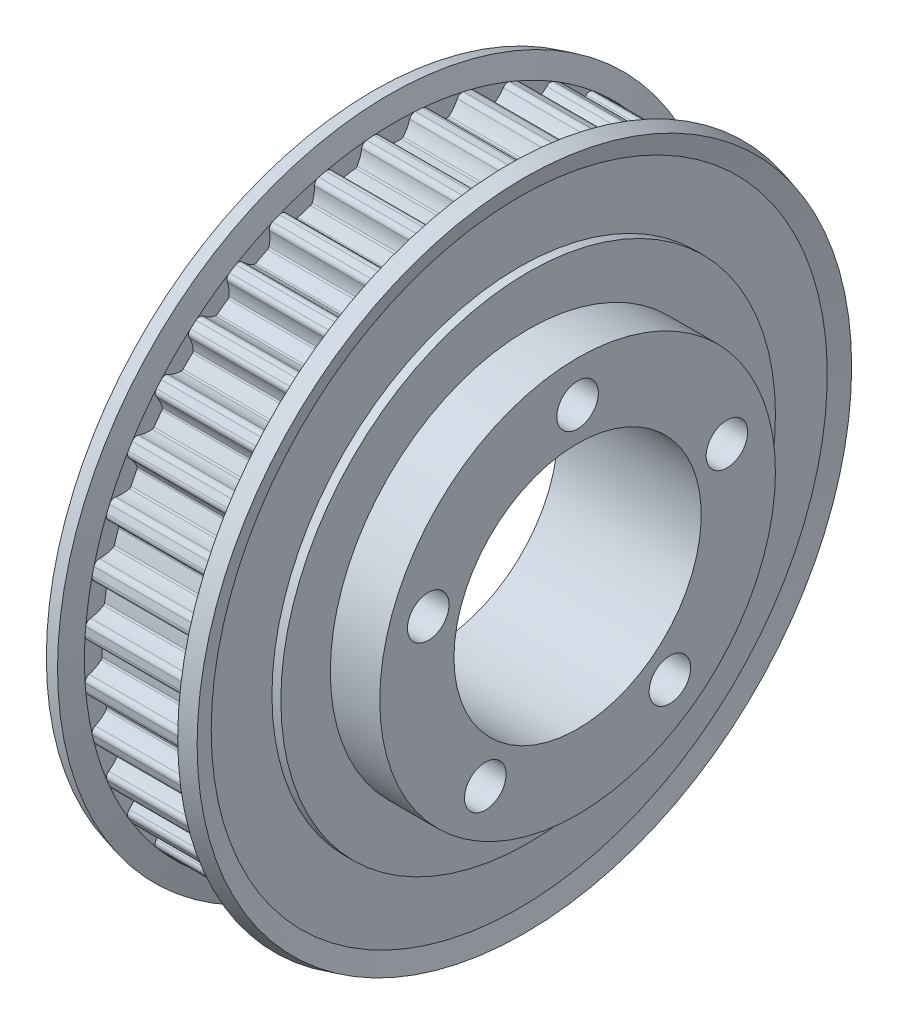
SolidWorks part; units mm, degrees
ref_plane "Front Plane" through (0, 0, 0) normal (0, 0, 1) x (1, 0, 0)
ref_plane "Top Plane" through (0, 0, 0) normal (0, 1, 0) x (1, 0, 0)
ref_plane "Right Plane" through (0, 0, 0) normal (1, 0, 0) x (0, 0, -1)
ref_plane "Plane1" through (0, 0, 0) normal (0, 0, 1) x (1, 0, 0)
sketch "Sketch1" plane through (0, 0, 0) normal (0, 0, 1) x (1, 0, 0)
  line L0 (0, 0) -> (0, 25)
  line L1 (0, 25) -> (0.9, 25)
  line L2 (0.9, 25) -> (0.9, 31.1394)
  line L3 (0.9, 31.1394) -> (0.3784, 33.0859)
  line L4 (0.3784, 33.0859) -> (1.9239, 33.5)
  line L5 (1.9239, 33.5) -> (2.5, 31.35)
  line L6 (2.5, 31.35) -> (13.5, 31.35)
  line L7 (13.5, 31.35) -> (14.0761, 33.5)
  line L8 (14.0761, 33.5) -> (15.6216, 33.0859)
  line L9 (15.6216, 33.0859) -> (15.1, 31.1394)
  line L10 (15.1, 31.1394) -> (15.1, 25)
  line L11 (15.1, 25) -> (16, 25)
  line L12 (16, 25) -> (16, 23.5)
  line L13 (16, 23.5) -> (21, 23.5)
  line L14 (21, 23.5) -> (21, 0)
  line L15 (21, 0) -> (0, 0)
  line L16 (21, 0) -> (0, 0) construction
revolve "Revolve1" add sketch "Sketch1" angle 360 about L16 reverse direction yes
ref_plane "Plane2" through (0, 0, 0) normal (0, 0, 1) x (1, 0, 0)
sketch "Sketch2" plane through (0, 0, 0) normal (0, 0, 1) x (1, 0, 0)
  line L0 (0, 0) -> (0, 12.5)
  line L1 (0, 12.5) -> (21, 12.5)
  line L2 (21, 12.5) -> (21, 0)
  line L3 (21, 0) -> (0, 0)
  line L4 (21, 0) -> (0, 0) construction
revolve "Cut-Revolve1" cut sketch "Sketch2" angle 360 about L4 reverse direction yes
ref_plane "Plane3" through (2.5, 0, 0) normal (1, 0, 0) x (0, 0, -1)
sketch "Sketch3" plane through (2.5, 0, 0) normal (1, 0, 0) x (0, 0, -1)
  line L0 (2.0877, 31.2804) -> (2.0877, 31.7615)
  line L1 (-2.0877, 31.7615) -> (-2.0877, 31.2804)
  arc A0 (-2.0877, 31.2804) -> (-1.5225, 30.8836) centre (-2.0511, 30.7316) cw
  arc A1 (-1.5225, 30.8836) -> (-0.8639, 29.6599) centre (1.625, 31.7885) ccw
  arc A2 (-0.8639, 29.6599) -> (-0.6683, 29.5725) centre (-0.6739, 29.8224) ccw
  arc A3 (-0.6683, 29.5725) -> (0.6683, 29.5725) centre (0, 0) cw
  arc A4 (0.6683, 29.5725) -> (0.8639, 29.6599) centre (0.6739, 29.8224) ccw
  arc A5 (0.8639, 29.6599) -> (1.5225, 30.8836) centre (-1.625, 31.7885) ccw
  arc A6 (1.5225, 30.8836) -> (2.0877, 31.2804) centre (2.0511, 30.7316) cw
  arc A7 (2.0877, 31.7615) -> (-2.0877, 31.7615) centre (0, 0) ccw
extrude "Cut-Extrude1" cut sketch "Sketch3" along normal blind 11
ref_plane "Plane4" through (2.5, 0, 0) normal (1, 0, 0) x (0, 0, -1)
sketch "Sketch4" plane through (2.5, 0, 0) normal (1, 0, 0) x (0, 0, -1)
  line L0 (6.9554, 30.5687) -> (7.0306, 31.0438)
  line L1 (2.9066, 31.697) -> (2.8313, 31.2219)
  arc A0 (2.8313, 31.2219) -> (3.3275, 30.7415) centre (2.7816, 30.6741) cw
  arc A1 (3.3275, 30.7415) -> (3.7865, 29.4299) centre (6.5778, 31.1429) ccw
  arc A2 (3.7865, 29.4299) -> (3.9661, 29.3129) centre (3.9996, 29.5606) ccw
  arc A3 (3.9661, 29.3129) -> (5.2862, 29.1038) centre (0, 0) cw
  arc A4 (5.2862, 29.1038) -> (5.4931, 29.1596) centre (5.3309, 29.3498) ccw
  arc A5 (5.4931, 29.1596) -> (6.335, 30.2652) centre (3.3678, 31.6513) ccw
  arc A6 (6.335, 30.2652) -> (6.9554, 30.5687) centre (6.8333, 30.0324) cw
  arc A7 (7.0306, 31.0438) -> (2.9066, 31.697) centre (0, 0) ccw
extrude "Cut-Extrude2" cut sketch "Sketch4" along normal blind 11
ref_plane "Plane5" through (2.5, 0, 0) normal (1, 0, 0) x (0, 0, -1)
sketch "Sketch5" plane through (2.5, 0, 0) normal (1, 0, 0) x (0, 0, -1)
  line L0 (11.6517, 29.1043) -> (11.8004, 29.5618)
  line L1 (7.8293, 30.8521) -> (7.6806, 30.3946)
  arc A0 (7.6806, 30.3946) -> (8.0956, 29.8425) centre (7.5459, 29.8613) cw
  arc A1 (8.0956, 29.8425) -> (8.3438, 28.4752) centre (11.3687, 29.7305) ccw
  arc A2 (8.3438, 28.4752) -> (8.5028, 28.3316) centre (8.5747, 28.571) ccw
  arc A3 (8.5028, 28.3316) -> (9.774, 27.9186) centre (0, 0) cw
  arc A4 (9.774, 27.9186) -> (9.987, 27.9413) centre (9.8566, 28.1545) ccw
  arc A5 (9.987, 27.9413) -> (10.9915, 28.9016) centre (8.2777, 30.7348) ccw
  arc A6 (10.9915, 28.9016) -> (11.6517, 29.1043) centre (11.4473, 28.5937) cw
  arc A7 (11.8004, 29.5618) -> (7.8293, 30.8521) centre (0, 0) ccw
extrude "Cut-Extrude3" cut sketch "Sketch5" along normal blind 11
ref_plane "Plane6" through (2.5, 0, 0) normal (1, 0, 0) x (0, 0, -1)
sketch "Sketch6" plane through (2.5, 0, 0) normal (1, 0, 0) x (0, 0, -1)
  line L0 (16.0612, 26.9232) -> (16.2796, 27.3519)
  line L1 (12.5592, 29.2475) -> (12.3408, 28.8189)
  arc A0 (12.3408, 28.8189) -> (12.6643, 28.2087) centre (12.1243, 28.3133) cw
  arc A1 (12.6643, 28.2087) -> (12.6956, 26.8194) centre (15.8796, 27.586) ccw
  arc A2 (12.6956, 26.8194) -> (12.8302, 26.6526) centre (12.9386, 26.8779) ccw
  arc A3 (12.8302, 26.6526) -> (14.021, 26.0459) centre (0, 0) cw
  arc A4 (14.021, 26.0459) -> (14.2351, 26.035) centre (14.1396, 26.266) ccw
  arc A5 (14.2351, 26.035) -> (15.3774, 26.8263) centre (12.9838, 29.0615) ccw
  arc A6 (15.3774, 26.8263) -> (16.0612, 26.9232) centre (15.7794, 26.4509) cw
  arc A7 (16.2796, 27.3519) -> (12.5592, 29.2475) centre (0, 0) ccw
extrude "Cut-Extrude4" cut sketch "Sketch6" along normal blind 11
ref_plane "Plane7" through (2.5, 0, 0) normal (1, 0, 0) x (0, 0, -1)
sketch "Sketch7" plane through (2.5, 0, 0) normal (1, 0, 0) x (0, 0, -1)
  line L0 (20.0752, 24.0793) -> (20.3579, 24.4684)
  line L1 (16.9799, 26.9227) -> (16.6972, 26.5335)
  arc A0 (16.6972, 26.5335) -> (16.9212, 25.8803) centre (16.4042, 26.068) cw
  arc A1 (16.9212, 25.8803) -> (16.7347, 24.5032) centre (19.9995, 24.7623) ccw
  arc A2 (16.7347, 24.5032) -> (16.8416, 24.3174) centre (16.9839, 24.5229) ccw
  arc A3 (16.8416, 24.3174) -> (17.9229, 23.5318) centre (0, 0) cw
  arc A4 (17.9229, 23.5318) -> (18.1326, 23.4876) centre (18.0744, 23.7307) ccw
  arc A5 (18.1326, 23.4876) -> (19.3847, 24.0904) centre (17.3702, 26.6726) ccw
  arc A6 (19.3847, 24.0904) -> (20.0752, 24.0793) centre (19.723, 23.6568) cw
  arc A7 (20.3579, 24.4684) -> (16.9799, 26.9227) centre (0, 0) ccw
extrude "Cut-Extrude5" cut sketch "Sketch7" along normal blind 11
ref_plane "Plane8" through (2.5, 0, 0) normal (1, 0, 0) x (0, 0, -1)
sketch "Sketch8" plane through (2.5, 0, 0) normal (1, 0, 0) x (0, 0, -1)
  line L0 (23.5948, 20.6423) -> (23.935, 20.9825)
  line L1 (20.9825, 23.935) -> (20.6423, 23.5948)
  arc A0 (20.6423, 23.5948) -> (20.7614, 22.9146) centre (20.2802, 23.1809) cw
  arc A1 (20.7614, 22.9146) -> (20.3618, 21.5836) centre (23.6269, 21.3288) ccw
  arc A2 (20.3618, 21.5836) -> (20.4383, 21.3834) centre (20.6111, 21.5641) ccw
  arc A3 (20.4383, 21.3834) -> (21.3834, 20.4383) centre (0, 0) cw
  arc A4 (21.3834, 20.4383) -> (21.5836, 20.3618) centre (21.5641, 20.6111) ccw
  arc A5 (21.5836, 20.3618) -> (22.9146, 20.7614) centre (21.3288, 23.6269) ccw
  arc A6 (22.9146, 20.7614) -> (23.5948, 20.6423) centre (23.1809, 20.2802) cw
  arc A7 (23.935, 20.9825) -> (20.9825, 23.935) centre (0, 0) ccw
extrude "Cut-Extrude6" cut sketch "Sketch8" along normal blind 11
ref_plane "Plane9" through (2.5, 0, 0) normal (1, 0, 0) x (0, 0, -1)
sketch "Sketch9" plane through (2.5, 0, 0) normal (1, 0, 0) x (0, 0, -1)
  line L0 (26.5335, 16.6972) -> (26.9227, 16.9799)
  line L1 (24.4684, 20.3579) -> (24.0793, 20.0752)
  arc A0 (24.0793, 20.0752) -> (24.0904, 19.3847) centre (23.6568, 19.723) cw
  arc A1 (24.0904, 19.3847) -> (23.4876, 18.1326) centre (26.6726, 17.3702) ccw
  arc A2 (23.4876, 18.1326) -> (23.5318, 17.9229) centre (23.7307, 18.0744) ccw
  arc A3 (23.5318, 17.9229) -> (24.3174, 16.8416) centre (0, 0) cw
  arc A4 (24.3174, 16.8416) -> (24.5032, 16.7347) centre (24.5229, 16.9839) ccw
  arc A5 (24.5032, 16.7347) -> (25.8803, 16.9212) centre (24.7623, 19.9995) ccw
  arc A6 (25.8803, 16.9212) -> (26.5335, 16.6972) centre (26.068, 16.4042) cw
  arc A7 (26.9227, 16.9799) -> (24.4684, 20.3579) centre (0, 0) ccw
extrude "Cut-Extrude7" cut sketch "Sketch9" along normal blind 11
ref_plane "Plane10" through (2.5, 0, 0) normal (1, 0, 0) x (0, 0, -1)
sketch "Sketch10" plane through (2.5, 0, 0) normal (1, 0, 0) x (0, 0, -1)
  line L0 (28.8189, 12.3408) -> (29.2475, 12.5592)
  line L1 (27.3519, 16.2796) -> (26.9232, 16.0612)
  arc A0 (26.9232, 16.0612) -> (26.8263, 15.3774) centre (26.4509, 15.7794) cw
  arc A1 (26.8263, 15.3774) -> (26.035, 14.2351) centre (29.0615, 12.9838) ccw
  arc A2 (26.035, 14.2351) -> (26.0459, 14.021) centre (26.266, 14.1396) ccw
  arc A3 (26.0459, 14.021) -> (26.6526, 12.8302) centre (0, 0) cw
  arc A4 (26.6526, 12.8302) -> (26.8194, 12.6956) centre (26.8779, 12.9386) ccw
  arc A5 (26.8194, 12.6956) -> (28.2087, 12.6643) centre (27.586, 15.8796) ccw
  arc A6 (28.2087, 12.6643) -> (28.8189, 12.3408) centre (28.3133, 12.1243) cw
  arc A7 (29.2475, 12.5592) -> (27.3519, 16.2796) centre (0, 0) ccw
extrude "Cut-Extrude8" cut sketch "Sketch10" along normal blind 11
ref_plane "Plane11" through (2.5, 0, 0) normal (1, 0, 0) x (0, 0, -1)
sketch "Sketch11" plane through (2.5, 0, 0) normal (1, 0, 0) x (0, 0, -1)
  line L0 (30.3946, 7.6806) -> (30.8521, 7.8293)
  line L1 (29.5618, 11.8004) -> (29.1043, 11.6517)
  arc A0 (29.1043, 11.6517) -> (28.9016, 10.9915) centre (28.5937, 11.4473) cw
  arc A1 (28.9016, 10.9915) -> (27.9413, 9.987) centre (30.7348, 8.2777) ccw
  arc A2 (27.9413, 9.987) -> (27.9186, 9.774) centre (28.1545, 9.8566) ccw
  arc A3 (27.9186, 9.774) -> (28.3316, 8.5028) centre (0, 0) cw
  arc A4 (28.3316, 8.5028) -> (28.4752, 8.3438) centre (28.571, 8.5747) ccw
  arc A5 (28.4752, 8.3438) -> (29.8425, 8.0956) centre (29.7305, 11.3687) ccw
  arc A6 (29.8425, 8.0956) -> (30.3946, 7.6806) centre (29.8613, 7.5459) cw
  arc A7 (30.8521, 7.8293) -> (29.5618, 11.8004) centre (0, 0) ccw
extrude "Cut-Extrude9" cut sketch "Sketch11" along normal blind 11
ref_plane "Plane12" through (2.5, 0, 0) normal (1, 0, 0) x (0, 0, -1)
sketch "Sketch12" plane through (2.5, 0, 0) normal (1, 0, 0) x (0, 0, -1)
  line L0 (31.2219, 2.8313) -> (31.697, 2.9066)
  line L1 (31.0438, 7.0306) -> (30.5687, 6.9554)
  arc A0 (30.5687, 6.9554) -> (30.2652, 6.335) centre (30.0324, 6.8333) cw
  arc A1 (30.2652, 6.335) -> (29.1596, 5.4931) centre (31.6513, 3.3678) ccw
  arc A2 (29.1596, 5.4931) -> (29.1038, 5.2862) centre (29.3498, 5.3309) ccw
  arc A3 (29.1038, 5.2862) -> (29.3129, 3.9661) centre (0, 0) cw
  arc A4 (29.3129, 3.9661) -> (29.4299, 3.7865) centre (29.5606, 3.9996) ccw
  arc A5 (29.4299, 3.7865) -> (30.7415, 3.3275) centre (31.1429, 6.5778) ccw
  arc A6 (30.7415, 3.3275) -> (31.2219, 2.8313) centre (30.6741, 2.7816) cw
  arc A7 (31.697, 2.9066) -> (31.0438, 7.0306) centre (0, 0) ccw
extrude "Cut-Extrude10" cut sketch "Sketch12" along normal blind 11
ref_plane "Plane13" through (2.5, 0, 0) normal (1, 0, 0) x (0, 0, -1)
sketch "Sketch13" plane through (2.5, 0, 0) normal (1, 0, 0) x (0, 0, -1)
  line L0 (31.2804, -2.0877) -> (31.7615, -2.0877)
  line L1 (31.7615, 2.0877) -> (31.2804, 2.0877)
  arc A0 (31.2804, 2.0877) -> (30.8836, 1.5225) centre (30.7316, 2.0511) cw
  arc A1 (30.8836, 1.5225) -> (29.6599, 0.8639) centre (31.7885, -1.625) ccw
  arc A2 (29.6599, 0.8639) -> (29.5725, 0.6683) centre (29.8224, 0.6739) ccw
  arc A3 (29.5725, 0.6683) -> (29.5725, -0.6683) centre (0, 0) cw
  arc A4 (29.5725, -0.6683) -> (29.6599, -0.8639) centre (29.8224, -0.6739) ccw
  arc A5 (29.6599, -0.8639) -> (30.8836, -1.5225) centre (31.7885, 1.625) ccw
  arc A6 (30.8836, -1.5225) -> (31.2804, -2.0877) centre (30.7316, -2.0511) cw
  arc A7 (31.7615, -2.0877) -> (31.7615, 2.0877) centre (0, 0) ccw
extrude "Cut-Extrude11" cut sketch "Sketch13" along normal blind 11
ref_plane "Plane14" through (2.5, 0, 0) normal (1, 0, 0) x (0, 0, -1)
sketch "Sketch14" plane through (2.5, 0, 0) normal (1, 0, 0) x (0, 0, -1)
  line L0 (30.5687, -6.9554) -> (31.0438, -7.0306)
  line L1 (31.697, -2.9066) -> (31.2219, -2.8313)
  arc A0 (31.2219, -2.8313) -> (30.7415, -3.3275) centre (30.6741, -2.7816) cw
  arc A1 (30.7415, -3.3275) -> (29.4299, -3.7865) centre (31.1429, -6.5778) ccw
  arc A2 (29.4299, -3.7865) -> (29.3129, -3.9661) centre (29.5606, -3.9996) ccw
  arc A3 (29.3129, -3.9661) -> (29.1038, -5.2862) centre (0, 0) cw
  arc A4 (29.1038, -5.2862) -> (29.1596, -5.4931) centre (29.3498, -5.3309) ccw
  arc A5 (29.1596, -5.4931) -> (30.2652, -6.335) centre (31.6513, -3.3678) ccw
  arc A6 (30.2652, -6.335) -> (30.5687, -6.9554) centre (30.0324, -6.8333) cw
  arc A7 (31.0438, -7.0306) -> (31.697, -2.9066) centre (0, 0) ccw
extrude "Cut-Extrude12" cut sketch "Sketch14" along normal blind 11
ref_plane "Plane15" through (2.5, 0, 0) normal (1, 0, 0) x (0, 0, -1)
sketch "Sketch15" plane through (2.5, 0, 0) normal (1, 0, 0) x (0, 0, -1)
  line L0 (29.1043, -11.6517) -> (29.5618, -11.8004)
  line L1 (30.8521, -7.8293) -> (30.3946, -7.6806)
  arc A0 (30.3946, -7.6806) -> (29.8425, -8.0956) centre (29.8613, -7.5459) cw
  arc A1 (29.8425, -8.0956) -> (28.4752, -8.3438) centre (29.7305, -11.3687) ccw
  arc A2 (28.4752, -8.3438) -> (28.3316, -8.5028) centre (28.571, -8.5747) ccw
  arc A3 (28.3316, -8.5028) -> (27.9186, -9.774) centre (0, 0) cw
  arc A4 (27.9186, -9.774) -> (27.9413, -9.987) centre (28.1545, -9.8566) ccw
  arc A5 (27.9413, -9.987) -> (28.9016, -10.9915) centre (30.7348, -8.2777) ccw
  arc A6 (28.9016, -10.9915) -> (29.1043, -11.6517) centre (28.5937, -11.4473) cw
  arc A7 (29.5618, -11.8004) -> (30.8521, -7.8293) centre (0, 0) ccw
extrude "Cut-Extrude13" cut sketch "Sketch15" along normal blind 11
ref_plane "Plane16" through (2.5, 0, 0) normal (1, 0, 0) x (0, 0, -1)
sketch "Sketch16" plane through (2.5, 0, 0) normal (1, 0, 0) x (0, 0, -1)
  line L0 (26.9232, -16.0612) -> (27.3519, -16.2796)
  line L1 (29.2475, -12.5592) -> (28.8189, -12.3408)
  arc A0 (28.8189, -12.3408) -> (28.2087, -12.6643) centre (28.3133, -12.1243) cw
  arc A1 (28.2087, -12.6643) -> (26.8194, -12.6956) centre (27.586, -15.8796) ccw
  arc A2 (26.8194, -12.6956) -> (26.6526, -12.8302) centre (26.8779, -12.9386) ccw
  arc A3 (26.6526, -12.8302) -> (26.0459, -14.021) centre (0, 0) cw
  arc A4 (26.0459, -14.021) -> (26.035, -14.2351) centre (26.266, -14.1396) ccw
  arc A5 (26.035, -14.2351) -> (26.8263, -15.3774) centre (29.0615, -12.9838) ccw
  arc A6 (26.8263, -15.3774) -> (26.9232, -16.0612) centre (26.4509, -15.7794) cw
  arc A7 (27.3519, -16.2796) -> (29.2475, -12.5592) centre (0, 0) ccw
extrude "Cut-Extrude14" cut sketch "Sketch16" along normal blind 11
ref_plane "Plane17" through (2.5, 0, 0) normal (1, 0, 0) x (0, 0, -1)
sketch "Sketch17" plane through (2.5, 0, 0) normal (1, 0, 0) x (0, 0, -1)
  line L0 (24.0793, -20.0752) -> (24.4684, -20.3579)
  line L1 (26.9227, -16.9799) -> (26.5335, -16.6972)
  arc A0 (26.5335, -16.6972) -> (25.8803, -16.9212) centre (26.068, -16.4042) cw
  arc A1 (25.8803, -16.9212) -> (24.5032, -16.7347) centre (24.7623, -19.9995) ccw
  arc A2 (24.5032, -16.7347) -> (24.3174, -16.8416) centre (24.5229, -16.9839) ccw
  arc A3 (24.3174, -16.8416) -> (23.5318, -17.9229) centre (0, 0) cw
  arc A4 (23.5318, -17.9229) -> (23.4876, -18.1326) centre (23.7307, -18.0744) ccw
  arc A5 (23.4876, -18.1326) -> (24.0904, -19.3847) centre (26.6726, -17.3702) ccw
  arc A6 (24.0904, -19.3847) -> (24.0793, -20.0752) centre (23.6568, -19.723) cw
  arc A7 (24.4684, -20.3579) -> (26.9227, -16.9799) centre (0, 0) ccw
extrude "Cut-Extrude15" cut sketch "Sketch17" along normal blind 11
ref_plane "Plane18" through (2.5, 0, 0) normal (1, 0, 0) x (0, 0, -1)
sketch "Sketch18" plane through (2.5, 0, 0) normal (1, 0, 0) x (0, 0, -1)
  line L0 (20.6423, -23.5948) -> (20.9825, -23.935)
  line L1 (23.935, -20.9825) -> (23.5948, -20.6423)
  arc A0 (23.5948, -20.6423) -> (22.9146, -20.7614) centre (23.1809, -20.2802) cw
  arc A1 (22.9146, -20.7614) -> (21.5836, -20.3618) centre (21.3288, -23.6269) ccw
  arc A2 (21.5836, -20.3618) -> (21.3834, -20.4383) centre (21.5641, -20.6111) ccw
  arc A3 (21.3834, -20.4383) -> (20.4383, -21.3834) centre (0, 0) cw
  arc A4 (20.4383, -21.3834) -> (20.3618, -21.5836) centre (20.6111, -21.5641) ccw
  arc A5 (20.3618, -21.5836) -> (20.7614, -22.9146) centre (23.6269, -21.3288) ccw
  arc A6 (20.7614, -22.9146) -> (20.6423, -23.5948) centre (20.2802, -23.1809) cw
  arc A7 (20.9825, -23.935) -> (23.935, -20.9825) centre (0, 0) ccw
extrude "Cut-Extrude16" cut sketch "Sketch18" along normal blind 11
ref_plane "Plane19" through (2.5, 0, 0) normal (1, 0, 0) x (0, 0, -1)
sketch "Sketch19" plane through (2.5, 0, 0) normal (1, 0, 0) x (0, 0, -1)
  line L0 (16.6972, -26.5335) -> (16.9799, -26.9227)
  line L1 (20.3579, -24.4684) -> (20.0752, -24.0793)
  arc A0 (20.0752, -24.0793) -> (19.3847, -24.0904) centre (19.723, -23.6568) cw
  arc A1 (19.3847, -24.0904) -> (18.1326, -23.4876) centre (17.3702, -26.6726) ccw
  arc A2 (18.1326, -23.4876) -> (17.9229, -23.5318) centre (18.0744, -23.7307) ccw
  arc A3 (17.9229, -23.5318) -> (16.8416, -24.3174) centre (0, 0) cw
  arc A4 (16.8416, -24.3174) -> (16.7347, -24.5032) centre (16.9839, -24.5229) ccw
  arc A5 (16.7347, -24.5032) -> (16.9212, -25.8803) centre (19.9995, -24.7623) ccw
  arc A6 (16.9212, -25.8803) -> (16.6972, -26.5335) centre (16.4042, -26.068) cw
  arc A7 (16.9799, -26.9227) -> (20.3579, -24.4684) centre (0, 0) ccw
extrude "Cut-Extrude17" cut sketch "Sketch19" along normal blind 11
ref_plane "Plane20" through (2.5, 0, 0) normal (1, 0, 0) x (0, 0, -1)
sketch "Sketch20" plane through (2.5, 0, 0) normal (1, 0, 0) x (0, 0, -1)
  line L0 (12.3408, -28.8189) -> (12.5592, -29.2475)
  line L1 (16.2796, -27.3519) -> (16.0612, -26.9232)
  arc A0 (16.0612, -26.9232) -> (15.3774, -26.8263) centre (15.7794, -26.4509) cw
  arc A1 (15.3774, -26.8263) -> (14.2351, -26.035) centre (12.9838, -29.0615) ccw
  arc A2 (14.2351, -26.035) -> (14.021, -26.0459) centre (14.1396, -26.266) ccw
  arc A3 (14.021, -26.0459) -> (12.8302, -26.6526) centre (0, 0) cw
  arc A4 (12.8302, -26.6526) -> (12.6956, -26.8194) centre (12.9386, -26.8779) ccw
  arc A5 (12.6956, -26.8194) -> (12.6643, -28.2087) centre (15.8796, -27.586) ccw
  arc A6 (12.6643, -28.2087) -> (12.3408, -28.8189) centre (12.1243, -28.3133) cw
  arc A7 (12.5592, -29.2475) -> (16.2796, -27.3519) centre (0, 0) ccw
extrude "Cut-Extrude18" cut sketch "Sketch20" along normal blind 11
ref_plane "Plane21" through (2.5, 0, 0) normal (1, 0, 0) x (0, 0, -1)
sketch "Sketch21" plane through (2.5, 0, 0) normal (1, 0, 0) x (0, 0, -1)
  line L0 (7.6806, -30.3946) -> (7.8293, -30.8521)
  line L1 (11.8004, -29.5618) -> (11.6517, -29.1043)
  arc A0 (11.6517, -29.1043) -> (10.9915, -28.9016) centre (11.4473, -28.5937) cw
  arc A1 (10.9915, -28.9016) -> (9.987, -27.9413) centre (8.2777, -30.7348) ccw
  arc A2 (9.987, -27.9413) -> (9.774, -27.9186) centre (9.8566, -28.1545) ccw
  arc A3 (9.774, -27.9186) -> (8.5028, -28.3316) centre (0, 0) cw
  arc A4 (8.5028, -28.3316) -> (8.3438, -28.4752) centre (8.5747, -28.571) ccw
  arc A5 (8.3438, -28.4752) -> (8.0956, -29.8425) centre (11.3687, -29.7305) ccw
  arc A6 (8.0956, -29.8425) -> (7.6806, -30.3946) centre (7.5459, -29.8613) cw
  arc A7 (7.8293, -30.8521) -> (11.8004, -29.5618) centre (0, 0) ccw
extrude "Cut-Extrude19" cut sketch "Sketch21" along normal blind 11
ref_plane "Plane22" through (2.5, 0, 0) normal (1, 0, 0) x (0, 0, -1)
sketch "Sketch22" plane through (2.5, 0, 0) normal (1, 0, 0) x (0, 0, -1)
  line L0 (2.8313, -31.2219) -> (2.9066, -31.697)
  line L1 (7.0306, -31.0438) -> (6.9554, -30.5687)
  arc A0 (6.9554, -30.5687) -> (6.335, -30.2652) centre (6.8333, -30.0324) cw
  arc A1 (6.335, -30.2652) -> (5.4931, -29.1596) centre (3.3678, -31.6513) ccw
  arc A2 (5.4931, -29.1596) -> (5.2862, -29.1038) centre (5.3309, -29.3498) ccw
  arc A3 (5.2862, -29.1038) -> (3.9661, -29.3129) centre (0, 0) cw
  arc A4 (3.9661, -29.3129) -> (3.7865, -29.4299) centre (3.9996, -29.5606) ccw
  arc A5 (3.7865, -29.4299) -> (3.3275, -30.7415) centre (6.5778, -31.1429) ccw
  arc A6 (3.3275, -30.7415) -> (2.8313, -31.2219) centre (2.7816, -30.6741) cw
  arc A7 (2.9066, -31.697) -> (7.0306, -31.0438) centre (0, 0) ccw
extrude "Cut-Extrude20" cut sketch "Sketch22" along normal blind 11
ref_plane "Plane23" through (2.5, 0, 0) normal (1, 0, 0) x (0, 0, -1)
sketch "Sketch23" plane through (2.5, 0, 0) normal (1, 0, 0) x (0, 0, -1)
  line L0 (-2.0877, -31.2804) -> (-2.0877, -31.7615)
  line L1 (2.0877, -31.7615) -> (2.0877, -31.2804)
  arc A0 (2.0877, -31.2804) -> (1.5225, -30.8836) centre (2.0511, -30.7316) cw
  arc A1 (1.5225, -30.8836) -> (0.8639, -29.6599) centre (-1.625, -31.7885) ccw
  arc A2 (0.8639, -29.6599) -> (0.6683, -29.5725) centre (0.6739, -29.8224) ccw
  arc A3 (0.6683, -29.5725) -> (-0.6683, -29.5725) centre (0, 0) cw
  arc A4 (-0.6683, -29.5725) -> (-0.8639, -29.6599) centre (-0.6739, -29.8224) ccw
  arc A5 (-0.8639, -29.6599) -> (-1.5225, -30.8836) centre (1.625, -31.7885) ccw
  arc A6 (-1.5225, -30.8836) -> (-2.0877, -31.2804) centre (-2.0511, -30.7316) cw
  arc A7 (-2.0877, -31.7615) -> (2.0877, -31.7615) centre (0, 0) ccw
extrude "Cut-Extrude21" cut sketch "Sketch23" along normal blind 11
ref_plane "Plane24" through (2.5, 0, 0) normal (1, 0, 0) x (0, 0, -1)
sketch "Sketch24" plane through (2.5, 0, 0) normal (1, 0, 0) x (0, 0, -1)
  line L0 (-6.9554, -30.5687) -> (-7.0306, -31.0438)
  line L1 (-2.9066, -31.697) -> (-2.8313, -31.2219)
  arc A0 (-2.8313, -31.2219) -> (-3.3275, -30.7415) centre (-2.7816, -30.6741) cw
  arc A1 (-3.3275, -30.7415) -> (-3.7865, -29.4299) centre (-6.5778, -31.1429) ccw
  arc A2 (-3.7865, -29.4299) -> (-3.9661, -29.3129) centre (-3.9996, -29.5606) ccw
  arc A3 (-3.9661, -29.3129) -> (-5.2862, -29.1038) centre (0, 0) cw
  arc A4 (-5.2862, -29.1038) -> (-5.4931, -29.1596) centre (-5.3309, -29.3498) ccw
  arc A5 (-5.4931, -29.1596) -> (-6.335, -30.2652) centre (-3.3678, -31.6513) ccw
  arc A6 (-6.335, -30.2652) -> (-6.9554, -30.5687) centre (-6.8333, -30.0324) cw
  arc A7 (-7.0306, -31.0438) -> (-2.9066, -31.697) centre (0, 0) ccw
extrude "Cut-Extrude22" cut sketch "Sketch24" along normal blind 11
ref_plane "Plane25" through (2.5, 0, 0) normal (1, 0, 0) x (0, 0, -1)
sketch "Sketch25" plane through (2.5, 0, 0) normal (1, 0, 0) x (0, 0, -1)
  line L0 (-11.6517, -29.1043) -> (-11.8004, -29.5618)
  line L1 (-7.8293, -30.8521) -> (-7.6806, -30.3946)
  arc A0 (-7.6806, -30.3946) -> (-8.0956, -29.8425) centre (-7.5459, -29.8613) cw
  arc A1 (-8.0956, -29.8425) -> (-8.3438, -28.4752) centre (-11.3687, -29.7305) ccw
  arc A2 (-8.3438, -28.4752) -> (-8.5028, -28.3316) centre (-8.5747, -28.571) ccw
  arc A3 (-8.5028, -28.3316) -> (-9.774, -27.9186) centre (0, 0) cw
  arc A4 (-9.774, -27.9186) -> (-9.987, -27.9413) centre (-9.8566, -28.1545) ccw
  arc A5 (-9.987, -27.9413) -> (-10.9915, -28.9016) centre (-8.2777, -30.7348) ccw
  arc A6 (-10.9915, -28.9016) -> (-11.6517, -29.1043) centre (-11.4473, -28.5937) cw
  arc A7 (-11.8004, -29.5618) -> (-7.8293, -30.8521) centre (0, 0) ccw
extrude "Cut-Extrude23" cut sketch "Sketch25" along normal blind 11
ref_plane "Plane26" through (2.5, 0, 0) normal (1, 0, 0) x (0, 0, -1)
sketch "Sketch26" plane through (2.5, 0, 0) normal (1, 0, 0) x (0, 0, -1)
  line L0 (-16.0612, -26.9232) -> (-16.2796, -27.3519)
  line L1 (-12.5592, -29.2475) -> (-12.3408, -28.8189)
  arc A0 (-12.3408, -28.8189) -> (-12.6643, -28.2087) centre (-12.1243, -28.3133) cw
  arc A1 (-12.6643, -28.2087) -> (-12.6956, -26.8194) centre (-15.8796, -27.586) ccw
  arc A2 (-12.6956, -26.8194) -> (-12.8302, -26.6526) centre (-12.9386, -26.8779) ccw
  arc A3 (-12.8302, -26.6526) -> (-14.021, -26.0459) centre (0, 0) cw
  arc A4 (-14.021, -26.0459) -> (-14.2351, -26.035) centre (-14.1396, -26.266) ccw
  arc A5 (-14.2351, -26.035) -> (-15.3774, -26.8263) centre (-12.9838, -29.0615) ccw
  arc A6 (-15.3774, -26.8263) -> (-16.0612, -26.9232) centre (-15.7794, -26.4509) cw
  arc A7 (-16.2796, -27.3519) -> (-12.5592, -29.2475) centre (0, 0) ccw
extrude "Cut-Extrude24" cut sketch "Sketch26" along normal blind 11
ref_plane "Plane27" through (2.5, 0, 0) normal (1, 0, 0) x (0, 0, -1)
sketch "Sketch27" plane through (2.5, 0, 0) normal (1, 0, 0) x (0, 0, -1)
  line L0 (-20.0752, -24.0793) -> (-20.3579, -24.4684)
  line L1 (-16.9799, -26.9227) -> (-16.6972, -26.5335)
  arc A0 (-16.6972, -26.5335) -> (-16.9212, -25.8803) centre (-16.4042, -26.068) cw
  arc A1 (-16.9212, -25.8803) -> (-16.7347, -24.5032) centre (-19.9995, -24.7623) ccw
  arc A2 (-16.7347, -24.5032) -> (-16.8416, -24.3174) centre (-16.9839, -24.5229) ccw
  arc A3 (-16.8416, -24.3174) -> (-17.9229, -23.5318) centre (0, 0) cw
  arc A4 (-17.9229, -23.5318) -> (-18.1326, -23.4876) centre (-18.0744, -23.7307) ccw
  arc A5 (-18.1326, -23.4876) -> (-19.3847, -24.0904) centre (-17.3702, -26.6726) ccw
  arc A6 (-19.3847, -24.0904) -> (-20.0752, -24.0793) centre (-19.723, -23.6568) cw
  arc A7 (-20.3579, -24.4684) -> (-16.9799, -26.9227) centre (0, 0) ccw
extrude "Cut-Extrude25" cut sketch "Sketch27" along normal blind 11
ref_plane "Plane28" through (2.5, 0, 0) normal (1, 0, 0) x (0, 0, -1)
sketch "Sketch28" plane through (2.5, 0, 0) normal (1, 0, 0) x (0, 0, -1)
  line L0 (-23.5948, -20.6423) -> (-23.935, -20.9825)
  line L1 (-20.9825, -23.935) -> (-20.6423, -23.5948)
  arc A0 (-20.6423, -23.5948) -> (-20.7614, -22.9146) centre (-20.2802, -23.1809) cw
  arc A1 (-20.7614, -22.9146) -> (-20.3618, -21.5836) centre (-23.6269, -21.3288) ccw
  arc A2 (-20.3618, -21.5836) -> (-20.4383, -21.3834) centre (-20.6111, -21.5641) ccw
  arc A3 (-20.4383, -21.3834) -> (-21.3834, -20.4383) centre (0, 0) cw
  arc A4 (-21.3834, -20.4383) -> (-21.5836, -20.3618) centre (-21.5641, -20.6111) ccw
  arc A5 (-21.5836, -20.3618) -> (-22.9146, -20.7614) centre (-21.3288, -23.6269) ccw
  arc A6 (-22.9146, -20.7614) -> (-23.5948, -20.6423) centre (-23.1809, -20.2802) cw
  arc A7 (-23.935, -20.9825) -> (-20.9825, -23.935) centre (0, 0) ccw
extrude "Cut-Extrude26" cut sketch "Sketch28" along normal blind 11
ref_plane "Plane29" through (2.5, 0, 0) normal (1, 0, 0) x (0, 0, -1)
sketch "Sketch29" plane through (2.5, 0, 0) normal (1, 0, 0) x (0, 0, -1)
  line L0 (-26.5335, -16.6972) -> (-26.9227, -16.9799)
  line L1 (-24.4684, -20.3579) -> (-24.0793, -20.0752)
  arc A0 (-24.0793, -20.0752) -> (-24.0904, -19.3847) centre (-23.6568, -19.723) cw
  arc A1 (-24.0904, -19.3847) -> (-23.4876, -18.1326) centre (-26.6726, -17.3702) ccw
  arc A2 (-23.4876, -18.1326) -> (-23.5318, -17.9229) centre (-23.7307, -18.0744) ccw
  arc A3 (-23.5318, -17.9229) -> (-24.3174, -16.8416) centre (0, 0) cw
  arc A4 (-24.3174, -16.8416) -> (-24.5032, -16.7347) centre (-24.5229, -16.9839) ccw
  arc A5 (-24.5032, -16.7347) -> (-25.8803, -16.9212) centre (-24.7623, -19.9995) ccw
  arc A6 (-25.8803, -16.9212) -> (-26.5335, -16.6972) centre (-26.068, -16.4042) cw
  arc A7 (-26.9227, -16.9799) -> (-24.4684, -20.3579) centre (0, 0) ccw
extrude "Cut-Extrude27" cut sketch "Sketch29" along normal blind 11
ref_plane "Plane30" through (2.5, 0, 0) normal (1, 0, 0) x (0, 0, -1)
sketch "Sketch30" plane through (2.5, 0, 0) normal (1, 0, 0) x (0, 0, -1)
  line L0 (-28.8189, -12.3408) -> (-29.2475, -12.5592)
  line L1 (-27.3519, -16.2796) -> (-26.9232, -16.0612)
  arc A0 (-26.9232, -16.0612) -> (-26.8263, -15.3774) centre (-26.4509, -15.7794) cw
  arc A1 (-26.8263, -15.3774) -> (-26.035, -14.2351) centre (-29.0615, -12.9838) ccw
  arc A2 (-26.035, -14.2351) -> (-26.0459, -14.021) centre (-26.266, -14.1396) ccw
  arc A3 (-26.0459, -14.021) -> (-26.6526, -12.8302) centre (0, 0) cw
  arc A4 (-26.6526, -12.8302) -> (-26.8194, -12.6956) centre (-26.8779, -12.9386) ccw
  arc A5 (-26.8194, -12.6956) -> (-28.2087, -12.6643) centre (-27.586, -15.8796) ccw
  arc A6 (-28.2087, -12.6643) -> (-28.8189, -12.3408) centre (-28.3133, -12.1243) cw
  arc A7 (-29.2475, -12.5592) -> (-27.3519, -16.2796) centre (0, 0) ccw
extrude "Cut-Extrude28" cut sketch "Sketch30" along normal blind 11
ref_plane "Plane31" through (2.5, 0, 0) normal (1, 0, 0) x (0, 0, -1)
sketch "Sketch31" plane through (2.5, 0, 0) normal (1, 0, 0) x (0, 0, -1)
  line L0 (-30.3946, -7.6806) -> (-30.8521, -7.8293)
  line L1 (-29.5618, -11.8004) -> (-29.1043, -11.6517)
  arc A0 (-29.1043, -11.6517) -> (-28.9016, -10.9915) centre (-28.5937, -11.4473) cw
  arc A1 (-28.9016, -10.9915) -> (-27.9413, -9.987) centre (-30.7348, -8.2777) ccw
  arc A2 (-27.9413, -9.987) -> (-27.9186, -9.774) centre (-28.1545, -9.8566) ccw
  arc A3 (-27.9186, -9.774) -> (-28.3316, -8.5028) centre (0, 0) cw
  arc A4 (-28.3316, -8.5028) -> (-28.4752, -8.3438) centre (-28.571, -8.5747) ccw
  arc A5 (-28.4752, -8.3438) -> (-29.8425, -8.0956) centre (-29.7305, -11.3687) ccw
  arc A6 (-29.8425, -8.0956) -> (-30.3946, -7.6806) centre (-29.8613, -7.5459) cw
  arc A7 (-30.8521, -7.8293) -> (-29.5618, -11.8004) centre (0, 0) ccw
extrude "Cut-Extrude29" cut sketch "Sketch31" along normal blind 11
ref_plane "Plane32" through (2.5, 0, 0) normal (1, 0, 0) x (0, 0, -1)
sketch "Sketch32" plane through (2.5, 0, 0) normal (1, 0, 0) x (0, 0, -1)
  line L0 (-31.2219, -2.8313) -> (-31.697, -2.9066)
  line L1 (-31.0438, -7.0306) -> (-30.5687, -6.9554)
  arc A0 (-30.5687, -6.9554) -> (-30.2652, -6.335) centre (-30.0324, -6.8333) cw
  arc A1 (-30.2652, -6.335) -> (-29.1596, -5.4931) centre (-31.6513, -3.3678) ccw
  arc A2 (-29.1596, -5.4931) -> (-29.1038, -5.2862) centre (-29.3498, -5.3309) ccw
  arc A3 (-29.1038, -5.2862) -> (-29.3129, -3.9661) centre (0, 0) cw
  arc A4 (-29.3129, -3.9661) -> (-29.4299, -3.7865) centre (-29.5606, -3.9996) ccw
  arc A5 (-29.4299, -3.7865) -> (-30.7415, -3.3275) centre (-31.1429, -6.5778) ccw
  arc A6 (-30.7415, -3.3275) -> (-31.2219, -2.8313) centre (-30.6741, -2.7816) cw
  arc A7 (-31.697, -2.9066) -> (-31.0438, -7.0306) centre (0, 0) ccw
extrude "Cut-Extrude30" cut sketch "Sketch32" along normal blind 11
ref_plane "Plane33" through (2.5, 0, 0) normal (1, 0, 0) x (0, 0, -1)
sketch "Sketch33" plane through (2.5, 0, 0) normal (1, 0, 0) x (0, 0, -1)
  line L0 (-31.2804, 2.0877) -> (-31.7615, 2.0877)
  line L1 (-31.7615, -2.0877) -> (-31.2804, -2.0877)
  arc A0 (-31.2804, -2.0877) -> (-30.8836, -1.5225) centre (-30.7316, -2.0511) cw
  arc A1 (-30.8836, -1.5225) -> (-29.6599, -0.8639) centre (-31.7885, 1.625) ccw
  arc A2 (-29.6599, -0.8639) -> (-29.5725, -0.6683) centre (-29.8224, -0.6739) ccw
  arc A3 (-29.5725, -0.6683) -> (-29.5725, 0.6683) centre (0, 0) cw
  arc A4 (-29.5725, 0.6683) -> (-29.6599, 0.8639) centre (-29.8224, 0.6739) ccw
  arc A5 (-29.6599, 0.8639) -> (-30.8836, 1.5225) centre (-31.7885, -1.625) ccw
  arc A6 (-30.8836, 1.5225) -> (-31.2804, 2.0877) centre (-30.7316, 2.0511) cw
  arc A7 (-31.7615, 2.0877) -> (-31.7615, -2.0877) centre (0, 0) ccw
extrude "Cut-Extrude31" cut sketch "Sketch33" along normal blind 11
ref_plane "Plane34" through (2.5, 0, 0) normal (1, 0, 0) x (0, 0, -1)
sketch "Sketch34" plane through (2.5, 0, 0) normal (1, 0, 0) x (0, 0, -1)
  line L0 (-30.5687, 6.9554) -> (-31.0438, 7.0306)
  line L1 (-31.697, 2.9066) -> (-31.2219, 2.8313)
  arc A0 (-31.2219, 2.8313) -> (-30.7415, 3.3275) centre (-30.6741, 2.7816) cw
  arc A1 (-30.7415, 3.3275) -> (-29.4299, 3.7865) centre (-31.1429, 6.5778) ccw
  arc A2 (-29.4299, 3.7865) -> (-29.3129, 3.9661) centre (-29.5606, 3.9996) ccw
  arc A3 (-29.3129, 3.9661) -> (-29.1038, 5.2862) centre (0, 0) cw
  arc A4 (-29.1038, 5.2862) -> (-29.1596, 5.4931) centre (-29.3498, 5.3309) ccw
  arc A5 (-29.1596, 5.4931) -> (-30.2652, 6.335) centre (-31.6513, 3.3678) ccw
  arc A6 (-30.2652, 6.335) -> (-30.5687, 6.9554) centre (-30.0324, 6.8333) cw
  arc A7 (-31.0438, 7.0306) -> (-31.697, 2.9066) centre (0, 0) ccw
extrude "Cut-Extrude32" cut sketch "Sketch34" along normal blind 11
ref_plane "Plane35" through (2.5, 0, 0) normal (1, 0, 0) x (0, 0, -1)
sketch "Sketch35" plane through (2.5, 0, 0) normal (1, 0, 0) x (0, 0, -1)
  line L0 (-29.1043, 11.6517) -> (-29.5618, 11.8004)
  line L1 (-30.8521, 7.8293) -> (-30.3946, 7.6806)
  arc A0 (-30.3946, 7.6806) -> (-29.8425, 8.0956) centre (-29.8613, 7.5459) cw
  arc A1 (-29.8425, 8.0956) -> (-28.4752, 8.3438) centre (-29.7305, 11.3687) ccw
  arc A2 (-28.4752, 8.3438) -> (-28.3316, 8.5028) centre (-28.571, 8.5747) ccw
  arc A3 (-28.3316, 8.5028) -> (-27.9186, 9.774) centre (0, 0) cw
  arc A4 (-27.9186, 9.774) -> (-27.9413, 9.987) centre (-28.1545, 9.8566) ccw
  arc A5 (-27.9413, 9.987) -> (-28.9016, 10.9915) centre (-30.7348, 8.2777) ccw
  arc A6 (-28.9016, 10.9915) -> (-29.1043, 11.6517) centre (-28.5937, 11.4473) cw
  arc A7 (-29.5618, 11.8004) -> (-30.8521, 7.8293) centre (0, 0) ccw
extrude "Cut-Extrude33" cut sketch "Sketch35" along normal blind 11
ref_plane "Plane36" through (2.5, 0, 0) normal (1, 0, 0) x (0, 0, -1)
sketch "Sketch36" plane through (2.5, 0, 0) normal (1, 0, 0) x (0, 0, -1)
  line L0 (-26.9232, 16.0612) -> (-27.3519, 16.2796)
  line L1 (-29.2475, 12.5592) -> (-28.8189, 12.3408)
  arc A0 (-28.8189, 12.3408) -> (-28.2087, 12.6643) centre (-28.3133, 12.1243) cw
  arc A1 (-28.2087, 12.6643) -> (-26.8194, 12.6956) centre (-27.586, 15.8796) ccw
  arc A2 (-26.8194, 12.6956) -> (-26.6526, 12.8302) centre (-26.8779, 12.9386) ccw
  arc A3 (-26.6526, 12.8302) -> (-26.0459, 14.021) centre (0, 0) cw
  arc A4 (-26.0459, 14.021) -> (-26.035, 14.2351) centre (-26.266, 14.1396) ccw
  arc A5 (-26.035, 14.2351) -> (-26.8263, 15.3774) centre (-29.0615, 12.9838) ccw
  arc A6 (-26.8263, 15.3774) -> (-26.9232, 16.0612) centre (-26.4509, 15.7794) cw
  arc A7 (-27.3519, 16.2796) -> (-29.2475, 12.5592) centre (0, 0) ccw
extrude "Cut-Extrude34" cut sketch "Sketch36" along normal blind 11
ref_plane "Plane37" through (2.5, 0, 0) normal (1, 0, 0) x (0, 0, -1)
sketch "Sketch37" plane through (2.5, 0, 0) normal (1, 0, 0) x (0, 0, -1)
  line L0 (-24.0793, 20.0752) -> (-24.4684, 20.3579)
  line L1 (-26.9227, 16.9799) -> (-26.5335, 16.6972)
  arc A0 (-26.5335, 16.6972) -> (-25.8803, 16.9212) centre (-26.068, 16.4042) cw
  arc A1 (-25.8803, 16.9212) -> (-24.5032, 16.7347) centre (-24.7623, 19.9995) ccw
  arc A2 (-24.5032, 16.7347) -> (-24.3174, 16.8416) centre (-24.5229, 16.9839) ccw
  arc A3 (-24.3174, 16.8416) -> (-23.5318, 17.9229) centre (0, 0) cw
  arc A4 (-23.5318, 17.9229) -> (-23.4876, 18.1326) centre (-23.7307, 18.0744) ccw
  arc A5 (-23.4876, 18.1326) -> (-24.0904, 19.3847) centre (-26.6726, 17.3702) ccw
  arc A6 (-24.0904, 19.3847) -> (-24.0793, 20.0752) centre (-23.6568, 19.723) cw
  arc A7 (-24.4684, 20.3579) -> (-26.9227, 16.9799) centre (0, 0) ccw
extrude "Cut-Extrude35" cut sketch "Sketch37" along normal blind 11
ref_plane "Plane38" through (2.5, 0, 0) normal (1, 0, 0) x (0, 0, -1)
sketch "Sketch38" plane through (2.5, 0, 0) normal (1, 0, 0) x (0, 0, -1)
  line L0 (-20.6423, 23.5948) -> (-20.9825, 23.935)
  line L1 (-23.935, 20.9825) -> (-23.5948, 20.6423)
  arc A0 (-23.5948, 20.6423) -> (-22.9146, 20.7614) centre (-23.1809, 20.2802) cw
  arc A1 (-22.9146, 20.7614) -> (-21.5836, 20.3618) centre (-21.3288, 23.6269) ccw
  arc A2 (-21.5836, 20.3618) -> (-21.3834, 20.4383) centre (-21.5641, 20.6111) ccw
  arc A3 (-21.3834, 20.4383) -> (-20.4383, 21.3834) centre (0, 0) cw
  arc A4 (-20.4383, 21.3834) -> (-20.3618, 21.5836) centre (-20.6111, 21.5641) ccw
  arc A5 (-20.3618, 21.5836) -> (-20.7614, 22.9146) centre (-23.6269, 21.3288) ccw
  arc A6 (-20.7614, 22.9146) -> (-20.6423, 23.5948) centre (-20.2802, 23.1809) cw
  arc A7 (-20.9825, 23.935) -> (-23.935, 20.9825) centre (0, 0) ccw
extrude "Cut-Extrude36" cut sketch "Sketch38" along normal blind 11
ref_plane "Plane39" through (2.5, 0, 0) normal (1, 0, 0) x (0, 0, -1)
sketch "Sketch39" plane through (2.5, 0, 0) normal (1, 0, 0) x (0, 0, -1)
  line L0 (-16.6972, 26.5335) -> (-16.9799, 26.9227)
  line L1 (-20.3579, 24.4684) -> (-20.0752, 24.0793)
  arc A0 (-20.0752, 24.0793) -> (-19.3847, 24.0904) centre (-19.723, 23.6568) cw
  arc A1 (-19.3847, 24.0904) -> (-18.1326, 23.4876) centre (-17.3702, 26.6726) ccw
  arc A2 (-18.1326, 23.4876) -> (-17.9229, 23.5318) centre (-18.0744, 23.7307) ccw
  arc A3 (-17.9229, 23.5318) -> (-16.8416, 24.3174) centre (0, 0) cw
  arc A4 (-16.8416, 24.3174) -> (-16.7347, 24.5032) centre (-16.9839, 24.5229) ccw
  arc A5 (-16.7347, 24.5032) -> (-16.9212, 25.8803) centre (-19.9995, 24.7623) ccw
  arc A6 (-16.9212, 25.8803) -> (-16.6972, 26.5335) centre (-16.4042, 26.068) cw
  arc A7 (-16.9799, 26.9227) -> (-20.3579, 24.4684) centre (0, 0) ccw
extrude "Cut-Extrude37" cut sketch "Sketch39" along normal blind 11
ref_plane "Plane40" through (2.5, 0, 0) normal (1, 0, 0) x (0, 0, -1)
sketch "Sketch40" plane through (2.5, 0, 0) normal (1, 0, 0) x (0, 0, -1)
  line L0 (-12.3408, 28.8189) -> (-12.5592, 29.2475)
  line L1 (-16.2796, 27.3519) -> (-16.0612, 26.9232)
  arc A0 (-16.0612, 26.9232) -> (-15.3774, 26.8263) centre (-15.7794, 26.4509) cw
  arc A1 (-15.3774, 26.8263) -> (-14.2351, 26.035) centre (-12.9838, 29.0615) ccw
  arc A2 (-14.2351, 26.035) -> (-14.021, 26.0459) centre (-14.1396, 26.266) ccw
  arc A3 (-14.021, 26.0459) -> (-12.8302, 26.6526) centre (0, 0) cw
  arc A4 (-12.8302, 26.6526) -> (-12.6956, 26.8194) centre (-12.9386, 26.8779) ccw
  arc A5 (-12.6956, 26.8194) -> (-12.6643, 28.2087) centre (-15.8796, 27.586) ccw
  arc A6 (-12.6643, 28.2087) -> (-12.3408, 28.8189) centre (-12.1243, 28.3133) cw
  arc A7 (-12.5592, 29.2475) -> (-16.2796, 27.3519) centre (0, 0) ccw
extrude "Cut-Extrude38" cut sketch "Sketch40" along normal blind 11
ref_plane "Plane41" through (2.5, 0, 0) normal (1, 0, 0) x (0, 0, -1)
sketch "Sketch41" plane through (2.5, 0, 0) normal (1, 0, 0) x (0, 0, -1)
  line L0 (-7.6806, 30.3946) -> (-7.8293, 30.8521)
  line L1 (-11.8004, 29.5618) -> (-11.6517, 29.1043)
  arc A0 (-11.6517, 29.1043) -> (-10.9915, 28.9016) centre (-11.4473, 28.5937) cw
  arc A1 (-10.9915, 28.9016) -> (-9.987, 27.9413) centre (-8.2777, 30.7348) ccw
  arc A2 (-9.987, 27.9413) -> (-9.774, 27.9186) centre (-9.8566, 28.1545) ccw
  arc A3 (-9.774, 27.9186) -> (-8.5028, 28.3316) centre (0, 0) cw
  arc A4 (-8.5028, 28.3316) -> (-8.3438, 28.4752) centre (-8.5747, 28.571) ccw
  arc A5 (-8.3438, 28.4752) -> (-8.0956, 29.8425) centre (-11.3687, 29.7305) ccw
  arc A6 (-8.0956, 29.8425) -> (-7.6806, 30.3946) centre (-7.5459, 29.8613) cw
  arc A7 (-7.8293, 30.8521) -> (-11.8004, 29.5618) centre (0, 0) ccw
extrude "Cut-Extrude39" cut sketch "Sketch41" along normal blind 11
ref_plane "Plane42" through (2.5, 0, 0) normal (1, 0, 0) x (0, 0, -1)
sketch "Sketch42" plane through (2.5, 0, 0) normal (1, 0, 0) x (0, 0, -1)
  line L0 (-2.8313, 31.2219) -> (-2.9066, 31.697)
  line L1 (-7.0306, 31.0438) -> (-6.9554, 30.5687)
  arc A0 (-6.9554, 30.5687) -> (-6.335, 30.2652) centre (-6.8333, 30.0324) cw
  arc A1 (-6.335, 30.2652) -> (-5.4931, 29.1596) centre (-3.3678, 31.6513) ccw
  arc A2 (-5.4931, 29.1596) -> (-5.2862, 29.1038) centre (-5.3309, 29.3498) ccw
  arc A3 (-5.2862, 29.1038) -> (-3.9661, 29.3129) centre (0, 0) cw
  arc A4 (-3.9661, 29.3129) -> (-3.7865, 29.4299) centre (-3.9996, 29.5606) ccw
  arc A5 (-3.7865, 29.4299) -> (-3.3275, 30.7415) centre (-6.5778, 31.1429) ccw
  arc A6 (-3.3275, 30.7415) -> (-2.8313, 31.2219) centre (-2.7816, 30.6741) cw
  arc A7 (-2.9066, 31.697) -> (-7.0306, 31.0438) centre (0, 0) ccw
extrude "Cut-Extrude40" cut sketch "Sketch42" along normal blind 11
sketch "Sketch43" plane through (0, 0, 0) normal (0, 0, 1) x (1, 0, 0)
  line L0 (0, 0) -> (21, 0) construction
  line L1 (21, -23.5) -> (21, 23.5) construction
  line L2 (16, -25) -> (16, 25) construction
  line L3 (21, 23.5) -> (16, 23.5)
  line L4 (21, 23.5) -> (21, 20)
  line L5 (21, 20) -> (16, 20)
  line L6 (16, 23.5) -> (16, 20)
  dimension "D1" = 40
revolve "Cut-Revolve2" cut sketch "Sketch43" angle 360 about L0
hole_wizard "M5x0.8 Tapped Hole1" positions "Sketch45" profile "Sketch46" tap size "M5x0.8" standard "ANSI Metric" end condition through all
sketch "Sketch45" plane through (21, 0, 0) normal (1, 0, 0) x (0, 0, -1)
  point P0 (0, 15.875)
  dimension "D1" = 15.875
sketch "Sketch46" plane through (21, 15.875, 0) normal (0, 1, 0) x (0, 0, -1)
  line L0 (0, 0) -> (0, 21)
  line L1 (0, 21) -> (2.1, 21)
  line L2 (2.1, 21) -> (2.1, 0)
  line L5 (2.1, 0) -> (0, 0)
  line L11 (0, -6.35) -> (0, 107.95) construction
  dimension "Thru Tap Drill Dia." = 4.2
  dimension "Thru Tap Drill Depth" = 21
cosmetic thread "Hole Thread1" parameters "D2"=5
pattern_circular "CirPattern1" count 5 over 360 about axis through (21, 0, 0) along (-1, 0, 0) of "M5x0.8 Tapped Hole1"
sketch "Sketch47" plane through (0, 0, 0) normal (-1, 0, 0) x (0, 0, 1)
  circle A0 centre (0, 0) radius 23.5
  dimension "D1" = 47
extrude "Cut-Extrude41" cut sketch "Sketch47" against normal blind 6.5
